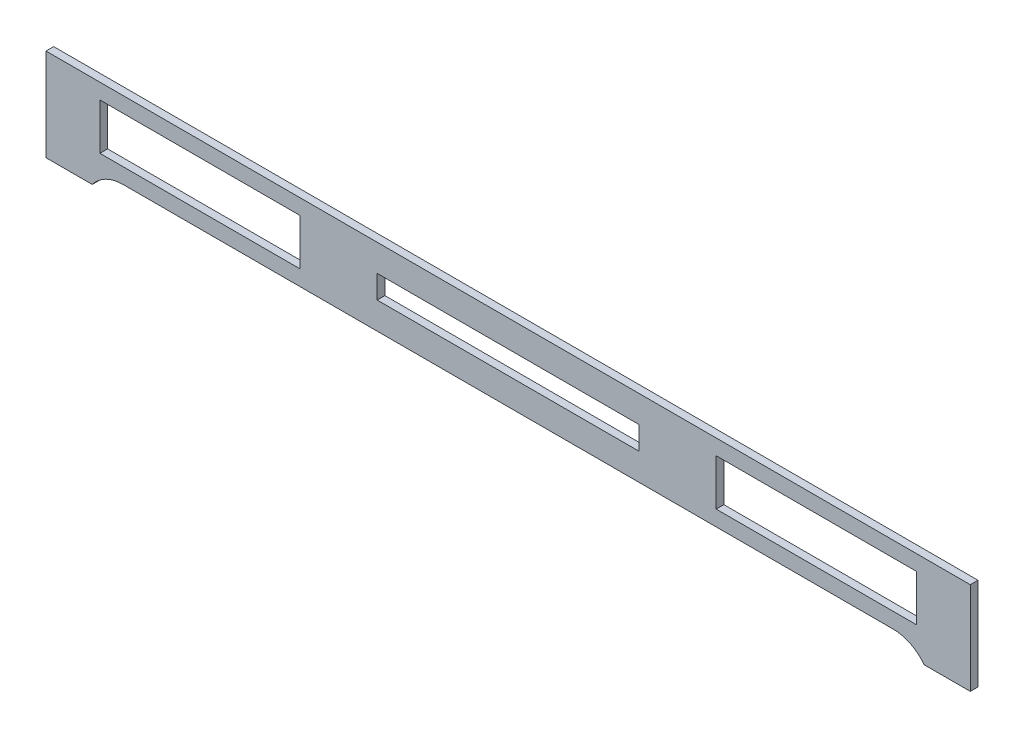
SolidWorks part; units mm, degrees
ref_plane "Front Plane" through (0, 0, 0) normal (0, 0, 1) x (1, 0, 0)
ref_plane "Top Plane" through (0, 0, 0) normal (0, 1, 0) x (1, 0, 0)
ref_plane "Right Plane" through (0, 0, 0) normal (1, 0, 0) x (0, 0, -1)
sketch "Sketch1" plane through (0, 0, 0) normal (0, 0, 1) x (1, 0, 0)
  line L0 (0, 0) -> (0, -10)
  line L1 (50, 0) -> (550, 0)
  line L2 (0, 0) -> (0, 50)
  line L3 (0, 50) -> (600, 50)
  line L4 (600, 0) -> (600, 50)
  line L5 (0, -10) -> (30, -10)
  line L6 (600, 0) -> (600, -10)
  line L7 (600, -10) -> (570, -10)
  arc A0 (30, -10) -> (50, 0) centre (50, -25) cw
  arc A1 (570, -10) -> (550, 0) centre (550, -25) ccw
  dimension "D7" = 25
  dimension "D8" = 25
  dimension "D1" = 600
  dimension "D2" = 50
  dimension "D3" = 10
  dimension "D4" = 10
  dimension "D5" = 30
  dimension "D6" = 30
  dimension "D9" = 10
  dimension "D10" = 10
extrude "Boss-Extrude1" add sketch "Sketch1" along normal blind 5
sketch "Sketch2" plane through (0, 0, 5) normal (0, 0, 1) x (1, 0, 0)
  line L0 (600, 50) -> (0, 50) construction
  line L1 (35, 40) -> (165, 40)
  line L2 (35, 40) -> (35, 10)
  line L3 (35, 10) -> (165, 10)
  line L4 (165, 40) -> (165, 10)
  line L5 (215, 32.5) -> (385, 32.5)
  line L6 (215, 32.5) -> (215, 17.5)
  line L7 (215, 17.5) -> (385, 17.5)
  line L8 (385, 32.5) -> (385, 17.5)
  line L9 (435, 40) -> (565, 40)
  line L10 (435, 40) -> (435, 10)
  line L11 (435, 10) -> (565, 10)
  line L12 (565, 40) -> (565, 10)
  line L13 (300, 50) -> (300, 0) construction
  line L14 (50, 0) -> (550, 0) construction
  point P12 (300, 32.5)
  point P15 (300, 50)
  point P16 (165, 25)
  point P17 (215, 25)
  point P18 (435, 25)
  point P21 (385, 25)
  point P22 (300, 25)
  point P23 (0, 0)
  point P26 (300, 0)
  dimension "D1" = 130
  dimension "D2" = 30
  dimension "D3" = 130
  dimension "D4" = 30
  dimension "D5" = 15
  dimension "D6" = 170
  dimension "D7" = 50
  dimension "D8" = 50
extrude "Cut-Extrude1" cut sketch "Sketch2" against normal through all
